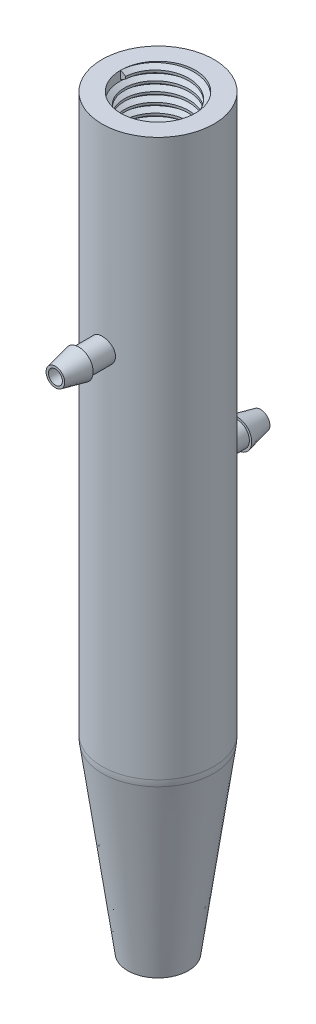
SolidWorks part; units mm, degrees
material "Glass"
ref_plane "Alzado" through (0, 0, 0) normal (0, 0, 1) x (1, 0, 0)
ref_plane "Planta" through (0, 0, 0) normal (0, 1, 0) x (1, 0, 0)
ref_plane "Vista lateral" through (0, 0, 0) normal (1, 0, 0) x (0, 0, -1)
sketch "Sketch1" plane through (0, 0, 0) normal (0, 0, 1) x (1, 0, 0)
  line L0 (-3.9534, -1.1854) -> (-1.25, -20.8464)
  line L1 (-1.25, -20.8464) -> (-3.25, -20.8464)
  line L2 (-3.25, -20.8464) -> (-5.9534, -1.1854)
  line L4 (-6, -0.5043) -> (-6, 59.1536)
  line L5 (-6, 59.1536) -> (-4, 59.1536)
  line L6 (-4, 59.1536) -> (-4, -0.5043)
  line L7 (0, 20) -> (0, -20.8464) construction
  line L8 (0, -55) -> (0, 55) construction
  arc A0 (-3.9534, -1.1854) -> (-4, -0.5043) centre (1, -0.5043) cw
  arc A1 (-5.9534, -1.1854) -> (-6, -0.5043) centre (-1, -0.5043) cw
  point P13 (-4, -0.8464)
  point P16 (-6, -0.8464)
  dimension "D6" = 5
  dimension "D1" = 60
  dimension "D2" = 2
  dimension "D3" = 20
  dimension "D4" = 1.25
  dimension "D5" = 4
  dimension "D7" = 2
revolve "Revolve2" add sketch "Sketch1" angle 360 about L7
sketch "Sketch2" plane through (0, 0, 0) normal (0, 0, 1) x (1, 0, 0)
  line L0 (0, -6.6) -> (0, 6.6) construction
  circle A0 centre (0, 23.1539) radius 0.75
  dimension "D1" = 1.5
thread "Thread1" pitch 1 method extrude profile "Thread Profile2" start angle 0, offset 0, length 10, pitch 1, diameter 8
ref_plane "Plane2" through (-4, 59.1536, 0) normal (0, 0, 1) x (-1, 0, 0)
sketch "Thread Profile2" plane through (-4, 59.1536, 0) normal (0, 0, 1) x (-1, 0, 0)
  line L0 (0, 0) -> (0, 1) construction
  line L11 (0, 0) -> (0, 0.875)
  line L12 (0, 0.875) -> (-0.5413, 0.5625)
  line L13 (-0.5413, 0.5625) -> (-0.5413, 0.3125)
  line L15 (-0.5413, 0.3125) -> (0, 0)
  line L17 (-0.5413, 0.4375) -> (0, 0.4375) construction
  point P2 (0, 0)
  dimension "Pitch" = 1
  dimension "Profile_Angle" = 60
  dimension "Profile_Land" = 0.25
  dimension "Profile_Height" = 0.5413
extrude "Cut-Extrude1" cut sketch "Sketch2" against normal blind 10
sketch "Sketch8" plane through (0, 0, 0) normal (1, 0, 0) x (0, 0, -1)
  line L0 (5.8, 23.9039) -> (11, 23.9039)
  line L1 (11, 23.9039) -> (11, 24.1539)
  line L2 (11, 24.1539) -> (8.5, 24.7039)
  line L3 (8.5, 24.7039) -> (8.5, 24.4539)
  line L4 (8.5, 24.4539) -> (5.8, 24.4539)
  line L7 (5.8, 24.4539) -> (5.8, 23.9039)
  line L8 (6, 23.9039) -> (6, 59.1536) construction
  line L9 (5.1517, 23.1539) -> (12.3503, 23.1539) construction
  dimension "D1" = 0.2
  dimension "D2" = 0.75
  dimension "D3" = 1.55
  dimension "D4" = 1.3
  dimension "D5" = 5.2
  dimension "D6" = 2.7
  dimension "D7" = 1
revolve "Revolve3" add sketch "Sketch8" angle 360 about L9
sketch "Sketch10" plane through (0, 0, 0) normal (0, 0, 1) x (1, 0, 0)
  line L0 (0, -9.35) -> (0, 9.35) construction
  line L1 (0, 23.1539) -> (11.7124, 23.1539) construction
  circle A0 centre (0, 38.1539) radius 0.75
  dimension "D1" = 1.5
  dimension "D2" = 15
extrude "Cut-Extrude2" cut sketch "Sketch10" along normal up to next
sketch "Sketch11" plane through (0, 0, 0) normal (1, 0, 0) x (0, 0, -1)
  line L0 (-4.5426, 38.1539) -> (-9.4792, 38.1539) construction
  line L1 (-5.8, 38.9039) -> (-11, 38.9039)
  line L2 (-11, 38.9039) -> (-11, 39.1539)
  line L3 (-11, 39.1539) -> (-8.5, 39.7039)
  line L4 (-8.5, 39.7039) -> (-8.5, 39.4539)
  line L5 (-8.5, 39.4539) -> (-5.8, 39.4539)
  line L6 (-5.8, 39.4539) -> (-5.8, 38.9039)
  line L7 (-6, 59.1536) -> (-6, 38.9039) construction
  dimension "D1" = 0.75
  dimension "D2" = 0.2
  dimension "D3" = 5.2
  dimension "D4" = 2.7
  dimension "D5" = 1.3
  dimension "D6" = 1.55
  dimension "D7" = 1
revolve "Revolve4" add sketch "Sketch11" angle 360 about L0
